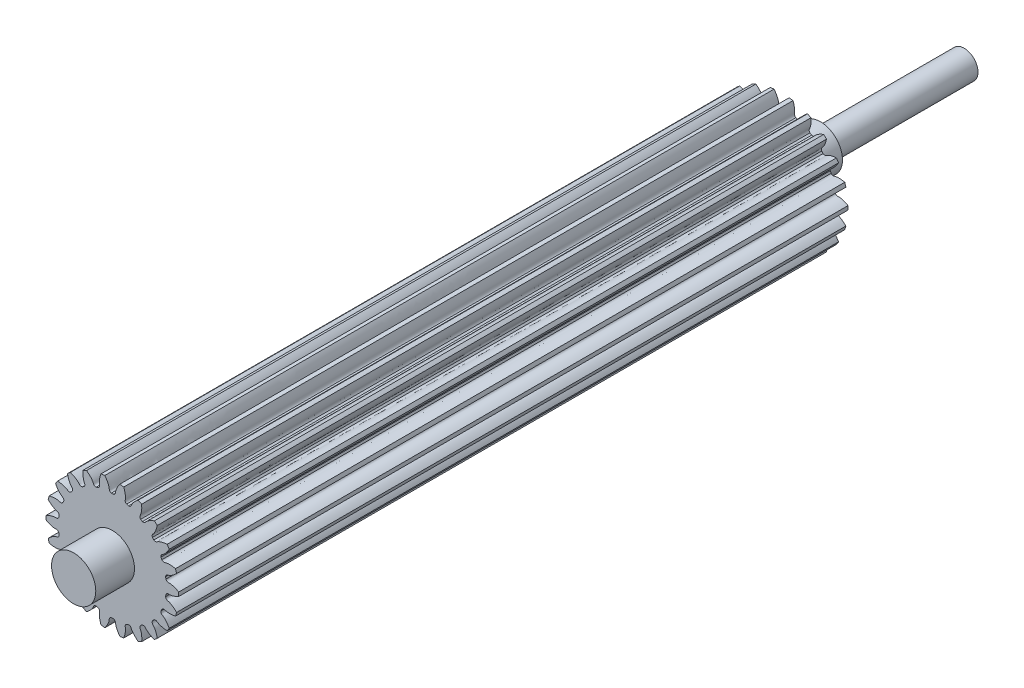
SolidWorks part; units mm, degrees
ref_plane "前视基准面" through (0, 0, 0) normal (0, 0, 1) x (1, 0, 0)
ref_plane "上视基准面" through (0, 0, 0) normal (0, 1, 0) x (1, 0, 0)
ref_plane "右视基准面" through (0, 0, 0) normal (1, 0, 0) x (0, 0, -1)
sketch "草图1" plane through (0, 0, 0) normal (0, 0, 1) x (1, 0, 0)
  circle A0 centre (0, 0) radius 12
extrude "凸台-拉伸1" add sketch "草图1" along normal blind 30
ref_axis "基准轴1" through (0, 0, -1.5) along (0, 0, 1)
sketch "草图2" plane through (0, 0, 0) normal (0, 0, 1) x (1, 0, 0)
  line L0 (0, 0) -> (0, 12) construction
  circle A0 centre (0, 0) radius 12 construction
  arc A1 (0.1857, 9.7482) -> (-0.1857, 9.7482) centre (0, 0) ccw
  arc A2 (3.0856, 13.5599) -> (-3.0856, 13.5599) centre (0, 0) ccw
  spline S0 degree 3 poles (0.1857, 9.7482) (0.5882, 9.8762) (0.5483, 10.1518) (0.5996, 10.4216) (0.606, 10.4519) (0.6139, 10.4862) (0.6235, 10.5243) (0.6349, 10.5661) (0.6484, 10.6117) (0.664, 10.661) (0.6819, 10.7139) (0.7023, 10.7703) (0.7253, 10.8301) (0.7511, 10.8933) (0.7797, 10.9597) (0.8114, 11.0293) (0.8462, 11.1021) (0.8843, 11.1778) (0.9259, 11.2563) (0.9711, 11.3377) (1.0199, 11.4217) (1.0726, 11.5082) (1.1292, 11.5972) (1.1899, 11.6884) (1.2547, 11.7818) (1.3238, 11.8773) (1.3973, 11.9746) (1.4753, 12.0737) (1.5579, 12.1744) (1.6452, 12.2766) (1.7372, 12.3802) (1.8341, 12.4849) (1.9359, 12.5906) (2.0428, 12.6972) (2.1547, 12.8044) (2.2718, 12.9123) (2.3942, 13.0205) (2.5218, 13.1289) (2.6548, 13.2373) (2.8415, 13.3834) (2.9864, 13.49) (3.0856, 13.5599) knots 0 0 0 0 0.157021 0.162531 0.168888 0.176093 0.184146 0.193046 0.202794 0.213389 0.224833 0.237123 0.250262 0.264248 0.279082 0.294763 0.311292 0.328669 0.346893 0.365965 0.385884 0.406652 0.428266 0.450729 0.474039 0.498197 0.523202 0.549055 0.575756 0.603304 0.6317 0.660944 0.691035 0.721974 0.75376 0.786395 0.819876 0.854206 0.889383 0.925408 1 1 1 1
  spline S1 degree 3 poles (-0.1857, 9.7482) (-0.5882, 9.8762) (-0.5483, 10.1518) (-0.5996, 10.4216) (-0.606, 10.4519) (-0.6139, 10.4862) (-0.6235, 10.5243) (-0.6349, 10.5661) (-0.6484, 10.6117) (-0.664, 10.661) (-0.6819, 10.7139) (-0.7023, 10.7703) (-0.7253, 10.8301) (-0.7511, 10.8933) (-0.7797, 10.9597) (-0.8114, 11.0293) (-0.8462, 11.1021) (-0.8843, 11.1778) (-0.9259, 11.2563) (-0.9711, 11.3377) (-1.0199, 11.4217) (-1.0726, 11.5082) (-1.1292, 11.5972) (-1.1899, 11.6884) (-1.2547, 11.7818) (-1.3238, 11.8773) (-1.3973, 11.9746) (-1.4753, 12.0737) (-1.5579, 12.1744) (-1.6452, 12.2766) (-1.7372, 12.3802) (-1.8341, 12.4849) (-1.9359, 12.5906) (-2.0428, 12.6972) (-2.1547, 12.8044) (-2.2718, 12.9123) (-2.3942, 13.0205) (-2.5218, 13.1289) (-2.6548, 13.2373) (-2.8415, 13.3834) (-2.9864, 13.49) (-3.0856, 13.5599) knots 0 0 0 0 0.157021 0.162531 0.168888 0.176093 0.184146 0.193046 0.202794 0.213389 0.224833 0.237123 0.250262 0.264248 0.279082 0.294763 0.311292 0.328669 0.346893 0.365965 0.385884 0.406652 0.428266 0.450729 0.474039 0.498197 0.523202 0.549055 0.575756 0.603304 0.6317 0.660944 0.691035 0.721974 0.75376 0.786395 0.819876 0.854206 0.889383 0.925408 1 1 1 1
extrude "切除-拉伸1" cut sketch "草图2" along normal through all
pattern_circular "阵列(圆周)1" count 22 every 16.364 about axis through (0, 0, -1.5) along (0, 0, 1) of "切除-拉伸1"
sketch "草图3" plane through (0, 0, 0) normal (0, 0, 1) x (1, 0, 0)
  circle A0 centre (0, 0) radius 11 construction
  dimension "Dn" = 22
sketch "草图4" plane through (0, 0, 0) normal (0, 0, -1) x (-1, 0, 0)
  arc A45 (2.9245, 9.3011) -> (2.5682, 9.4057) centre (0, 0) ccw
  arc A46 (2.0557, 11.8226) -> (1.3584, 11.9229) centre (0, 0) ccw
  arc A47 (0.1857, 9.7482) -> (-0.1857, 9.7482) centre (0, 0) ccw
  arc A48 (-1.3584, 11.9229) -> (-2.0557, 11.8226) centre (0, 0) ccw
  arc A49 (-2.5682, 9.4057) -> (-2.9245, 9.3011) centre (0, 0) ccw
  arc A50 (-4.6624, 11.0572) -> (-5.3032, 10.7646) centre (0, 0) ccw
  arc A51 (-5.1141, 8.3011) -> (-5.4265, 8.1004) centre (0, 0) ccw
  arc A52 (-7.5887, 9.2958) -> (-8.1211, 8.8344) centre (0, 0) ccw
  arc A53 (-7.2456, 6.5241) -> (-7.4888, 6.2434) centre (0, 0) ccw
  arc A54 (-9.9003, 6.7812) -> (-10.2811, 6.1886) centre (0, 0) ccw
  arc A55 (-8.7902, 4.2184) -> (-8.9444, 3.8807) centre (0, 0) ccw
  arc A56 (-11.4097, 3.7173) -> (-11.6082, 3.0414) centre (0, 0) ccw
  arc A57 (-9.6226, 1.5711) -> (-9.6754, 1.2035) centre (0, 0) ccw
  arc A58 (-11.9948, 0.3522) -> (-11.9948, -0.3522) centre (0, 0) ccw
  arc A59 (-9.6754, -1.2035) -> (-9.6226, -1.5711) centre (0, 0) ccw
  arc A60 (-11.6082, -3.0414) -> (-11.4097, -3.7173) centre (0, 0) ccw
  arc A61 (-8.9444, -3.8807) -> (-8.7902, -4.2184) centre (0, 0) ccw
  arc A62 (-10.2811, -6.1886) -> (-9.9003, -6.7812) centre (0, 0) ccw
  arc A63 (-7.4888, -6.2434) -> (-7.2456, -6.5241) centre (0, 0) ccw
  arc A64 (-8.1211, -8.8344) -> (-7.5887, -9.2958) centre (0, 0) ccw
  arc A65 (-5.4265, -8.1004) -> (-5.1141, -8.3011) centre (0, 0) ccw
  arc A66 (-5.3032, -10.7646) -> (-4.6624, -11.0572) centre (0, 0) ccw
  arc A67 (-2.9245, -9.3011) -> (-2.5682, -9.4057) centre (0, 0) ccw
  arc A68 (-2.0557, -11.8226) -> (-1.3584, -11.9229) centre (0, 0) ccw
  arc A69 (-0.1857, -9.7482) -> (0.1857, -9.7482) centre (0, 0) ccw
  arc A70 (1.3584, -11.9229) -> (2.0557, -11.8226) centre (0, 0) ccw
  arc A71 (2.5682, -9.4057) -> (2.9245, -9.3011) centre (0, 0) ccw
  arc A72 (4.6624, -11.0572) -> (5.3032, -10.7646) centre (0, 0) ccw
  arc A73 (5.1141, -8.3011) -> (5.4265, -8.1004) centre (0, 0) ccw
  arc A74 (7.5887, -9.2958) -> (8.1211, -8.8344) centre (0, 0) ccw
  arc A75 (7.2456, -6.5241) -> (7.4888, -6.2434) centre (0, 0) ccw
  arc A76 (9.9003, -6.7812) -> (10.2811, -6.1886) centre (0, 0) ccw
  arc A77 (8.7902, -4.2184) -> (8.9444, -3.8807) centre (0, 0) ccw
  arc A78 (11.4097, -3.7173) -> (11.6082, -3.0414) centre (0, 0) ccw
  arc A79 (9.6226, -1.5711) -> (9.6754, -1.2035) centre (0, 0) ccw
  arc A80 (11.9948, -0.3522) -> (11.9948, 0.3522) centre (0, 0) ccw
  arc A81 (9.6754, 1.2035) -> (9.6226, 1.5711) centre (0, 0) ccw
  arc A82 (11.6082, 3.0414) -> (11.4097, 3.7173) centre (0, 0) ccw
  arc A83 (8.9444, 3.8807) -> (8.7902, 4.2184) centre (0, 0) ccw
  arc A84 (10.2811, 6.1886) -> (9.9003, 6.7812) centre (0, 0) ccw
  arc A85 (7.4888, 6.2434) -> (7.2456, 6.5241) centre (0, 0) ccw
  arc A86 (8.1211, 8.8344) -> (7.5887, 9.2958) centre (0, 0) ccw
  arc A87 (5.4265, 8.1004) -> (5.1141, 8.3011) centre (0, 0) ccw
  arc A88 (5.3032, 10.7646) -> (4.6624, 11.0572) centre (0, 0) ccw
  arc A89 (2.9245, 9.3011) -> (2.5682, 9.4057) centre (0, 0) ccw
  arc A90 (2.0557, 11.8226) -> (1.3584, 11.9229) centre (0, 0) ccw
  arc A91 (0.1857, 9.7482) -> (-0.1857, 9.7482) centre (0, 0) ccw
  arc A92 (-1.3584, 11.9229) -> (-2.0557, 11.8226) centre (0, 0) ccw
  arc A93 (-2.5682, 9.4057) -> (-2.9245, 9.3011) centre (0, 0) ccw
  arc A94 (-4.6624, 11.0572) -> (-5.3032, 10.7646) centre (0, 0) ccw
  arc A95 (-5.1141, 8.3011) -> (-5.4265, 8.1004) centre (0, 0) ccw
  arc A96 (-7.5887, 9.2958) -> (-8.1211, 8.8344) centre (0, 0) ccw
  arc A97 (-7.2456, 6.5241) -> (-7.4888, 6.2434) centre (0, 0) ccw
  arc A98 (-9.9003, 6.7812) -> (-10.2811, 6.1886) centre (0, 0) ccw
  arc A99 (-8.7902, 4.2184) -> (-8.9444, 3.8807) centre (0, 0) ccw
  arc A100 (-11.4097, 3.7173) -> (-11.6082, 3.0414) centre (0, 0) ccw
  arc A101 (-9.6226, 1.5711) -> (-9.6754, 1.2035) centre (0, 0) ccw
  arc A102 (-11.9948, 0.3522) -> (-11.9948, -0.3522) centre (0, 0) ccw
  arc A103 (-9.6754, -1.2035) -> (-9.6226, -1.5711) centre (0, 0) ccw
  arc A104 (-11.6082, -3.0414) -> (-11.4097, -3.7173) centre (0, 0) ccw
  arc A105 (-8.9444, -3.8807) -> (-8.7902, -4.2184) centre (0, 0) ccw
  arc A106 (-10.2811, -6.1886) -> (-9.9003, -6.7812) centre (0, 0) ccw
  arc A107 (-7.4888, -6.2434) -> (-7.2456, -6.5241) centre (0, 0) ccw
  arc A108 (-8.1211, -8.8344) -> (-7.5887, -9.2958) centre (0, 0) ccw
  arc A109 (-5.4265, -8.1004) -> (-5.1141, -8.3011) centre (0, 0) ccw
  arc A110 (-5.3032, -10.7646) -> (-4.6624, -11.0572) centre (0, 0) ccw
  arc A111 (-2.9245, -9.3011) -> (-2.5682, -9.4057) centre (0, 0) ccw
  arc A112 (-2.0557, -11.8226) -> (-1.3584, -11.9229) centre (0, 0) ccw
  arc A113 (-0.1857, -9.7482) -> (0.1857, -9.7482) centre (0, 0) ccw
  arc A114 (1.3584, -11.9229) -> (2.0557, -11.8226) centre (0, 0) ccw
  arc A115 (2.5682, -9.4057) -> (2.9245, -9.3011) centre (0, 0) ccw
  arc A116 (4.6624, -11.0572) -> (5.3032, -10.7646) centre (0, 0) ccw
  arc A117 (5.1141, -8.3011) -> (5.4265, -8.1004) centre (0, 0) ccw
  arc A118 (7.5887, -9.2958) -> (8.1211, -8.8344) centre (0, 0) ccw
  arc A119 (7.2456, -6.5241) -> (7.4888, -6.2434) centre (0, 0) ccw
  arc A120 (9.9003, -6.7812) -> (10.2811, -6.1886) centre (0, 0) ccw
  arc A121 (8.7902, -4.2184) -> (8.9444, -3.8807) centre (0, 0) ccw
  arc A122 (11.4097, -3.7173) -> (11.6082, -3.0414) centre (0, 0) ccw
  arc A123 (9.6226, -1.5711) -> (9.6754, -1.2035) centre (0, 0) ccw
  arc A124 (11.9948, -0.3522) -> (11.9948, 0.3522) centre (0, 0) ccw
  arc A125 (9.6754, 1.2035) -> (9.6226, 1.5711) centre (0, 0) ccw
  arc A126 (11.6082, 3.0414) -> (11.4097, 3.7173) centre (0, 0) ccw
  arc A127 (8.9444, 3.8807) -> (8.7902, 4.2184) centre (0, 0) ccw
  arc A128 (10.2811, 6.1886) -> (9.9003, 6.7812) centre (0, 0) ccw
  arc A129 (7.4888, 6.2434) -> (7.2456, 6.5241) centre (0, 0) ccw
  arc A130 (8.1211, 8.8344) -> (7.5887, 9.2958) centre (0, 0) ccw
  arc A131 (5.4265, 8.1004) -> (5.1141, 8.3011) centre (0, 0) ccw
  arc A132 (5.3032, 10.7646) -> (4.6624, 11.0572) centre (0, 0) ccw
  spline S44 degree 3 poles (-7496.4592, 2789.5016) (226.4744, -158.9957) (28.5821, 31.5473) (4.2738, 10.7434) (4.1283, 10.6084) (3.9999, 10.4794) (3.888, 10.3576) (3.7917, 10.2441) (3.7102, 10.1398) (3.6518, 10.0587) (3.6037, 9.9872) (3.5713, 9.9359) (3.5381, 9.8795) (3.5167, 9.8409) (0.6369, 4.2172) (43.7494, -24.3223) (-6732.0995, 4323.7051) knots -19.040021 -19.040021 -19.040021 -19.040021 0.549271 0.593348 0.634035 0.671331 0.705237 0.735752 0.762877 0.786611 0.797206 0.815854 0.823907 0.837469 0.842979 4.709556 4.709556 4.709556 4.709556 only from (4.6624, 11.0572) to (2.9245, 9.3011)
  spline S45 degree 3 poles (7999.956, -2.3149) (-49.9496, 3.1915) (1.7443, 3.8923) (2.3619, 10.18) (2.3658, 10.2385) (2.3681, 10.3211) (2.3668, 10.4204) (2.3608, 10.536) (2.3486, 10.6678) (2.329, 10.8154) (2.3007, 10.9784) (2.2624, 11.1562) (2.213, 11.3485) (2.1511, 11.5544) (-8.9188, 43.6975) (-289.9121, -23.2582) (7822.5066, -1669.0431) knots -3.709393 -3.709393 -3.709393 -3.709393 0.157021 0.162531 0.176093 0.193046 0.213389 0.237123 0.264248 0.294763 0.328669 0.365965 0.406652 0.450729 0.498197 21.310868 21.310868 21.310868 21.310868 only from (2.5682, 9.4057) to (2.0557, 11.8226)
  spline S46 degree 3 poles (-7978.6933, 564.5106) (262.0949, -88.75) (18.5364, 38.3219) (1.0739, 11.5123) (0.9723, 11.3417) (0.8855, 11.1818) (0.8124, 11.0334) (0.752, 10.8973) (0.7032, 10.7743) (0.6701, 10.6801) (0.644, 10.5979) (0.6274, 10.5396) (0.6113, 10.4761) (0.6018, 10.4331) (-0.577, 4.2258) (48.8297, -11.0115) (-7677.5306, 2251.913) knots -19.040021 -19.040021 -19.040021 -19.040021 0.549271 0.593348 0.634035 0.671331 0.705237 0.735752 0.762877 0.786611 0.797206 0.815854 0.823907 0.837469 0.842979 4.709556 4.709556 4.709556 4.709556 only from (1.3584, 11.9229) to (0.1857, 9.7482)
  spline S47 degree 3 poles (7676.5537, 2251.6269) (-48.8255, -11.0102) (0.577, 4.2261) (-0.6018, 10.4331) (-0.6145, 10.4903) (-0.6356, 10.5702) (-0.6648, 10.6651) (-0.7032, 10.7743) (-0.752, 10.8973) (-0.8124, 11.0334) (-0.8855, 11.1818) (-0.9723, 11.3417) (-1.0739, 11.5123) (-1.1913, 11.6924) (-20.8685, 39.4148) (-271.616, -103.9938) (7975.8639, 602.4197) knots -3.709393 -3.709393 -3.709393 -3.709393 0.157021 0.162531 0.176093 0.193046 0.213389 0.237123 0.264248 0.294763 0.328669 0.365965 0.406652 0.450729 0.498197 21.310868 21.310868 21.310868 21.310868 only from (-0.1857, 9.7482) to (-1.3584, 11.9229)
  spline S48 degree 3 poles (-7814.5412, -1706.2138) (276.482, -11.3143) (6.989, 41.9919) (-2.213, 11.3485) (-2.2624, 11.1562) (-2.3007, 10.9784) (-2.329, 10.8154) (-2.3486, 10.6678) (-2.3608, 10.536) (-2.366, 10.4362) (-2.3678, 10.3501) (-2.3674, 10.2894) (-2.3649, 10.224) (-2.3619, 10.18) (-1.7442, 3.8921) (49.954, 3.1915) (-8000.9739, -2.3156) knots -19.040021 -19.040021 -19.040021 -19.040021 0.549271 0.593348 0.634035 0.671331 0.705237 0.735752 0.762877 0.786611 0.797206 0.815854 0.823907 0.837469 0.842979 4.709556 4.709556 4.709556 4.709556 only from (-2.0557, 11.8226) to (-2.5682, 9.4057)
  spline S49 degree 3 poles (6731.2428, 4323.1553) (-43.7458, -24.3199) (-0.637, 4.2175) (-3.5167, 9.8409) (-3.5451, 9.8922) (-3.5879, 9.963) (-3.6426, 10.0458) (-3.7102, 10.1398) (-3.7917, 10.2441) (-3.888, 10.3576) (-3.9999, 10.4794) (-4.1283, 10.6084) (-4.2738, 10.7434) (-4.4372, 10.8832) (-31.1276, 31.9389) (-231.3152, -176.3044) (7483.0641, 2825.078) knots -3.709393 -3.709393 -3.709393 -3.709393 0.157021 0.162531 0.176093 0.193046 0.213389 0.237123 0.264248 0.294763 0.328669 0.365965 0.406652 0.450729 0.498197 21.310868 21.310868 21.310868 21.310868 only from (-2.9245, 9.3011) to (-4.6624, 11.0572)
  spline S50 degree 3 poles (-7017.3014, -3838.7108) (268.4701, 67.0379) (-5.1246, 42.26) (-5.3206, 10.2653) (-5.3138, 10.0669) (-5.3004, 9.8855) (-5.2817, 9.7211) (-5.2589, 9.574) (-5.2335, 9.4441) (-5.2104, 9.3469) (-5.1879, 9.2637) (-5.1704, 9.2057) (-5.1495, 9.1436) (-5.1343, 9.1022) (-2.7701, 3.243) (47.0314, 17.1359) (-7676.2259, -2256.3566) knots -19.040021 -19.040021 -19.040021 -19.040021 0.549271 0.593348 0.634035 0.671331 0.705237 0.735752 0.762877 0.786611 0.797206 0.815854 0.823907 0.837469 0.842979 4.709556 4.709556 4.709556 4.709556 only from (-5.3032, 10.7646) to (-5.1141, 8.3011)
  spline S51 degree 3 poles (5240.6065, 6044.4474) (-35.1221, -35.6594) (-1.7994, 3.8672) (-6.1468, 8.4515) (-6.1884, 8.4928) (-6.2494, 8.5486) (-6.3253, 8.6126) (-6.4166, 8.6838) (-6.5242, 8.7609) (-6.6486, 8.8427) (-6.7903, 8.928) (-6.9498, 9.0156) (-7.1274, 9.1041) (-7.3236, 9.1923) (-38.865, 21.8754) (-172.2747, -234.3319) (6384.031, 4818.8653) knots -3.709393 -3.709393 -3.709393 -3.709393 0.157021 0.162531 0.176093 0.193046 0.213389 0.237123 0.264248 0.294763 0.328669 0.365965 0.406652 0.450729 0.498197 21.310868 21.310868 21.310868 21.310868 only from (-5.4265, 8.1004) to (-7.5887, 9.2958)
  spline S52 degree 3 poles (-5651.5616, -5660.2183) (238.7084, 139.9592) (-16.823, 39.1044) (-7.9971, 8.3505) (-7.9348, 8.1621) (-7.8708, 7.9917) (-7.8065, 7.8393) (-7.7432, 7.7046) (-7.6822, 7.5871) (-7.6327, 7.5003) (-7.5876, 7.4269) (-7.5545, 7.3761) (-7.517, 7.3224) (-7.4907, 7.287) (-3.5716, 2.3312) (40.2985, 29.692) (-6729.5957, -4327.6011) knots -19.040021 -19.040021 -19.040021 -19.040021 0.549271 0.593348 0.634035 0.671331 0.705237 0.735752 0.762877 0.786611 0.797206 0.815854 0.823907 0.837469 0.842979 4.709556 4.709556 4.709556 4.709556 only from (-8.1211, 8.8344) to (-7.2456, 6.5241)
  spline S53 degree 3 poles (3325.4075, 7276.0543) (-23.653, -44.11) (-2.816, 3.2036) (-8.2789, 6.3774) (-8.3304, 6.4053) (-8.4047, 6.4416) (-8.4955, 6.4817) (-8.6032, 6.5243) (-8.7281, 6.5679) (-8.8705, 6.6114) (-9.0305, 6.6533) (-9.2082, 6.6924) (-9.4036, 6.7273) (-9.6167, 6.7566) (-43.4537, 10.0398) (-99.2774, -273.3752) (4767.8017, 6422.2568) knots -3.709393 -3.709393 -3.709393 -3.709393 0.157021 0.162531 0.176093 0.193046 0.213389 0.237123 0.264248 0.294763 0.328669 0.365965 0.406652 0.450729 0.498197 21.310868 21.310868 21.310868 21.310868 only from (-7.4888, 6.2434) to (-9.9003, 6.7812)
  spline S54 degree 3 poles (-3827.9659, -7023.1686) (189.608, 201.5418) (-27.1586, 32.7808) (-10.0258, 5.7592) (-9.9129, 5.596) (-9.8035, 5.4506) (-9.6989, 5.3224) (-9.6002, 5.211) (-9.5086, 5.1155) (-9.4366, 5.0462) (-9.3727, 4.9884) (-9.3266, 4.949) (-9.2755, 4.908) (-9.2403, 4.8814) (-4.0837, 1.2306) (30.3009, 39.8427) (-5237.7736, -6048.249) knots -19.040021 -19.040021 -19.040021 -19.040021 0.549271 0.593348 0.634035 0.671331 0.705237 0.735752 0.762877 0.786611 0.797206 0.815854 0.823907 0.837469 0.842979 4.709556 4.709556 4.709556 4.709556 only from (-10.2811, 6.1886) to (-8.7902, 4.2184)
  spline S55 degree 3 poles (1140.8038, 7918.1985) (-10.2676, -48.987) (-3.6045, 2.2804) (-9.7402, 3.7867) (-9.7976, 3.7989) (-9.8791, 3.8128) (-9.9775, 3.8257) (-10.0928, 3.8362) (-10.225, 3.8429) (-10.3738, 3.8445) (-10.5392, 3.8396) (-10.7207, 3.8271) (-10.918, 3.8055) (-11.1307, 3.7736) (-44.522, -2.6092) (-18.2373, -290.2712) (2765.3134, 7505.3552) knots -3.709393 -3.709393 -3.709393 -3.709393 0.157021 0.162531 0.176093 0.193046 0.213389 0.237123 0.264248 0.294763 0.328669 0.365965 0.406652 0.450729 0.498197 21.310868 21.310868 21.310868 21.310868 only from (-8.9444, 3.8807) to (-11.4097, 3.7173)
  spline S56 degree 3 poles (-1694.2511, -7817.1435) (125.1466, 246.7967) (-35.2939, 23.8015) (-11.2422, 2.7013) (-11.0879, 2.5765) (-10.942, 2.4678) (-10.8055, 2.3743) (-10.6794, 2.2952) (-10.5646, 2.2294) (-10.476, 2.1832) (-10.3984, 2.1457) (-10.3431, 2.1209) (-10.2825, 2.096) (-10.2412, 2.0804) (-4.2649, 0.0302) (17.8486, 46.7655) (-3321.6183, -7278.9038) knots -19.040021 -19.040021 -19.040021 -19.040021 0.549271 0.593348 0.634035 0.671331 0.705237 0.735752 0.762877 0.786611 0.797206 0.815854 0.823907 0.837469 0.842979 4.709556 4.709556 4.709556 4.709556 only from (-11.6082, 3.0414) to (-9.6226, 1.5711)
  spline S57 degree 3 poles (-1136.2211, 7918.8574) (3.9495, -49.8954) (-4.101, 1.1726) (-10.4125, 0.8891) (-10.4709, 0.8847) (-10.5531, 0.8751) (-10.6512, 0.8598) (-10.7647, 0.8373) (-10.8934, 0.8065) (-11.0367, 0.7661) (-11.194, 0.7149) (-11.3647, 0.6517) (-11.5479, 0.5754) (-11.743, 0.4849) (-41.9835, -15.0468) (64.2803, -283.6512) (538.7958, 7980.4144) knots -3.709393 -3.709393 -3.709393 -3.709393 0.157021 0.162531 0.176093 0.193046 0.213389 0.237123 0.264248 0.294763 0.328669 0.365965 0.406652 0.450729 0.498197 21.310868 21.310868 21.310868 21.310868 only from (-9.6754, 1.2035) to (-11.9948, 0.3522)
  spline S58 degree 3 poles (576.7218, -7977.82) (50.5467, 272.0576) (-40.5699, 12.894) (-11.5479, -0.5754) (-11.3647, -0.6517) (-11.194, -0.7149) (-11.0367, -0.7661) (-10.8934, -0.8065) (-10.7647, -0.8373) (-10.6667, -0.8567) (-10.5817, -0.8708) (-10.5216, -0.879) (-10.4565, -0.8858) (-10.4125, -0.8891) (-4.1007, -1.1726) (3.9502, 49.8997) (-1136.3653, -7919.8651) knots -19.040021 -19.040021 -19.040021 -19.040021 0.549271 0.593348 0.634035 0.671331 0.705237 0.735752 0.762877 0.786611 0.797206 0.815854 0.823907 0.837469 0.842979 4.709556 4.709556 4.709556 4.709556 only from (-11.9948, -0.3522) to (-9.6754, -1.2035)
  spline S59 degree 3 poles (-3321.1961, 7277.9776) (17.8467, -46.7616) (-4.2652, -0.0303) (-10.2412, -2.0804) (-10.296, -2.1012) (-10.3722, -2.1335) (-10.4619, -2.1758) (-10.5646, -2.2294) (-10.6794, -2.2952) (-10.8055, -2.3743) (-10.942, -2.4678) (-11.0879, -2.5765) (-11.2422, -2.7014) (-11.4039, -2.8432) (-36.0437, -26.2654) (141.5903, -254.0515) (-1731.3717, 7808.9478) knots -3.709393 -3.709393 -3.709393 -3.709393 0.157021 0.162531 0.176093 0.193046 0.213389 0.237123 0.264248 0.294763 0.328669 0.365965 0.406652 0.450729 0.498197 21.310868 21.310868 21.310868 21.310868 only from (-9.6226, -1.5711) to (-11.6082, -3.0414)
  spline S60 degree 3 poles (2800.9721, -7492.1809) (-28.1483, 275.278) (-42.5592, 0.9418) (-10.918, -3.8055) (-10.7207, -3.8271) (-10.5392, -3.8396) (-10.3738, -3.8445) (-10.225, -3.8429) (-10.0928, -3.8362) (-9.9933, -3.8272) (-9.9078, -3.8167) (-9.8478, -3.8076) (-9.7834, -3.7958) (-9.7402, -3.7867) (-3.6042, -2.2804) (-10.2682, 48.9913) (1140.9493, -7919.206) knots -19.040021 -19.040021 -19.040021 -19.040021 0.549271 0.593348 0.634035 0.671331 0.705237 0.735752 0.762877 0.786611 0.797206 0.815854 0.823907 0.837469 0.842979 4.709556 4.709556 4.709556 4.709556 only from (-11.4097, -3.7173) to (-8.9444, -3.8807)
  spline S61 degree 3 poles (-5237.1076, 6047.4793) (30.2981, -39.8394) (-4.0839, -1.2307) (-9.2403, -4.8814) (-9.287, -4.9168) (-9.351, -4.9692) (-9.4251, -5.0352) (-9.5086, -5.1155) (-9.6002, -5.211) (-9.6989, -5.3224) (-9.8035, -5.4506) (-9.9129, -5.596) (-10.0258, -5.7592) (-10.1409, -5.9408) (-27.1838, -35.3562) (207.4295, -203.8701) (-3861.2738, 7004.8468) knots -3.709393 -3.709393 -3.709393 -3.709393 0.157021 0.162531 0.176093 0.193046 0.213389 0.237123 0.264248 0.294763 0.328669 0.365965 0.406652 0.450729 0.498197 21.310868 21.310868 21.310868 21.310868 only from (-8.7902, -4.2184) to (-10.2811, -6.1886)
  spline S62 degree 3 poles (4798.3044, -6399.5699) (-104.5629, 256.197) (-41.1006, -11.0867) (-9.4036, -6.7273) (-9.2082, -6.6924) (-9.0305, -6.6533) (-8.8705, -6.6114) (-8.7281, -6.5679) (-8.6032, -6.5243) (-8.5102, -6.4876) (-8.4311, -6.4535) (-8.3761, -6.4279) (-8.3177, -6.3984) (-8.2789, -6.3774) (-2.8158, -3.2034) (-23.6547, 44.114) (3325.831, -7276.9799) knots -19.040021 -19.040021 -19.040021 -19.040021 0.549271 0.593348 0.634035 0.671331 0.705237 0.735752 0.762877 0.786611 0.797206 0.815854 0.823907 0.837469 0.842979 4.709556 4.709556 4.709556 4.709556 only from (-9.9003, -6.7812) to (-7.4888, -6.2434)
  spline S63 degree 3 poles (-6728.7397, 4327.0502) (40.2948, -29.6897) (-3.5717, -2.3314) (-7.4907, -7.287) (-7.5256, -7.3341) (-7.5722, -7.4024) (-7.6248, -7.4866) (-7.6822, -7.5871) (-7.7432, -7.7046) (-7.8065, -7.8393) (-7.8708, -7.9917) (-7.9348, -8.1621) (-7.9971, -8.3505) (-8.0564, -8.5572) (-16.1217, -41.5826) (256.4639, -137.1723) (-5678.3585, 5633.2547) knots -3.709393 -3.709393 -3.709393 -3.709393 0.157021 0.162531 0.176093 0.193046 0.213389 0.237123 0.264248 0.294763 0.328669 0.365965 0.406652 0.450729 0.498197 21.310868 21.310868 21.310868 21.310868 only from (-7.2456, -6.5241) to (-8.1211, -8.8344)
  spline S64 degree 3 poles (6406.9065, -4788.5038) (-172.5064, 216.3604) (-36.3122, -22.2169) (-7.1274, -9.1041) (-6.9498, -9.0156) (-6.7903, -8.928) (-6.6486, -8.8427) (-6.5242, -8.7609) (-6.4166, -8.6838) (-6.3378, -8.6224) (-6.2715, -8.5674) (-6.2259, -8.5273) (-6.1781, -8.4826) (-6.1468, -8.4515) (-1.7992, -3.867) (-35.1249, 35.6627) (5241.2736, -6045.2162) knots -19.040021 -19.040021 -19.040021 -19.040021 0.549271 0.593348 0.634035 0.671331 0.705237 0.735752 0.762877 0.786611 0.797206 0.815854 0.823907 0.837469 0.842979 4.709556 4.709556 4.709556 4.709556 only from (-7.5887, -9.2958) to (-5.4265, -8.1004)
  spline S65 degree 3 poles (-7675.2494, 2256.0692) (47.0272, -17.1347) (-2.7702, -3.2433) (-5.1343, -9.1022) (-5.1545, -9.1572) (-5.18, -9.2359) (-5.2067, -9.3315) (-5.2335, -9.4441) (-5.2589, -9.574) (-5.2817, -9.7211) (-5.3004, -9.8855) (-5.3138, -10.0669) (-5.3206, -10.2653) (-5.3192, -10.4804) (-3.7535, -44.4402) (284.7212, -59.3616) (-7035.4164, 3805.2899) knots -3.709393 -3.709393 -3.709393 -3.709393 0.157021 0.162531 0.176093 0.193046 0.213389 0.237123 0.264248 0.294763 0.328669 0.365965 0.406652 0.450729 0.498197 21.310868 21.310868 21.310868 21.310868 only from (-5.1141, -8.3011) to (-5.3032, -10.7646)
  spline S66 degree 3 poles (7496.4592, -2789.5016) (-226.4744, 158.9957) (-28.5821, -31.5473) (-4.2738, -10.7434) (-4.1283, -10.6084) (-3.9999, -10.4794) (-3.888, -10.3576) (-3.7917, -10.2441) (-3.7102, -10.1398) (-3.6518, -10.0587) (-3.6037, -9.9872) (-3.5713, -9.9359) (-3.5381, -9.8795) (-3.5167, -9.8409) (-0.6369, -4.2172) (-43.7494, 24.3223) (6732.0995, -4323.7051) knots -19.040021 -19.040021 -19.040021 -19.040021 0.549271 0.593348 0.634035 0.671331 0.705237 0.735752 0.762877 0.786611 0.797206 0.815854 0.823907 0.837469 0.842979 4.709556 4.709556 4.709556 4.709556 only from (-4.6624, -11.0572) to (-2.9245, -9.3011)
  spline S67 degree 3 poles (-7999.956, 2.3149) (49.9496, -3.1915) (-1.7443, -3.8923) (-2.3619, -10.18) (-2.3658, -10.2385) (-2.3681, -10.3211) (-2.3668, -10.4204) (-2.3608, -10.536) (-2.3486, -10.6678) (-2.329, -10.8154) (-2.3007, -10.9784) (-2.2624, -11.1562) (-2.213, -11.3485) (-2.1511, -11.5544) (8.9188, -43.6975) (289.9121, 23.2582) (-7822.5066, 1669.0431) knots -3.709393 -3.709393 -3.709393 -3.709393 0.157021 0.162531 0.176093 0.193046 0.213389 0.237123 0.264248 0.294763 0.328669 0.365965 0.406652 0.450729 0.498197 21.310868 21.310868 21.310868 21.310868 only from (-2.5682, -9.4057) to (-2.0557, -11.8226)
  spline S68 degree 3 poles (7978.6933, -564.5106) (-262.0949, 88.75) (-18.5364, -38.3219) (-1.0739, -11.5123) (-0.9723, -11.3417) (-0.8855, -11.1818) (-0.8124, -11.0334) (-0.752, -10.8973) (-0.7032, -10.7743) (-0.6701, -10.6801) (-0.644, -10.5979) (-0.6274, -10.5396) (-0.6113, -10.4761) (-0.6018, -10.4331) (0.577, -4.2258) (-48.8297, 11.0115) (7677.5306, -2251.913) knots -19.040021 -19.040021 -19.040021 -19.040021 0.549271 0.593348 0.634035 0.671331 0.705237 0.735752 0.762877 0.786611 0.797206 0.815854 0.823907 0.837469 0.842979 4.709556 4.709556 4.709556 4.709556 only from (-1.3584, -11.9229) to (-0.1857, -9.7482)
  spline S69 degree 3 poles (-7676.5537, -2251.6269) (48.8255, 11.0102) (-0.577, -4.2261) (0.6018, -10.4331) (0.6145, -10.4903) (0.6356, -10.5702) (0.6648, -10.6651) (0.7032, -10.7743) (0.752, -10.8973) (0.8124, -11.0334) (0.8855, -11.1818) (0.9723, -11.3417) (1.0739, -11.5123) (1.1913, -11.6924) (20.8685, -39.4148) (271.616, 103.9938) (-7975.8639, -602.4197) knots -3.709393 -3.709393 -3.709393 -3.709393 0.157021 0.162531 0.176093 0.193046 0.213389 0.237123 0.264248 0.294763 0.328669 0.365965 0.406652 0.450729 0.498197 21.310868 21.310868 21.310868 21.310868 only from (0.1857, -9.7482) to (1.3584, -11.9229)
  spline S70 degree 3 poles (7814.5412, 1706.2138) (-276.482, 11.3143) (-6.989, -41.9919) (2.213, -11.3485) (2.2624, -11.1562) (2.3007, -10.9784) (2.329, -10.8154) (2.3486, -10.6678) (2.3608, -10.536) (2.366, -10.4362) (2.3678, -10.3501) (2.3674, -10.2894) (2.3649, -10.224) (2.3619, -10.18) (1.7442, -3.8921) (-49.954, -3.1915) (8000.9739, 2.3156) knots -19.040021 -19.040021 -19.040021 -19.040021 0.549271 0.593348 0.634035 0.671331 0.705237 0.735752 0.762877 0.786611 0.797206 0.815854 0.823907 0.837469 0.842979 4.709556 4.709556 4.709556 4.709556 only from (2.0557, -11.8226) to (2.5682, -9.4057)
  spline S71 degree 3 poles (-6731.2428, -4323.1553) (43.7458, 24.3199) (0.637, -4.2175) (3.5167, -9.8409) (3.5451, -9.8922) (3.5879, -9.963) (3.6426, -10.0458) (3.7102, -10.1398) (3.7917, -10.2441) (3.888, -10.3576) (3.9999, -10.4794) (4.1283, -10.6084) (4.2738, -10.7434) (4.4372, -10.8832) (31.1276, -31.9389) (231.3152, 176.3044) (-7483.0641, -2825.078) knots -3.709393 -3.709393 -3.709393 -3.709393 0.157021 0.162531 0.176093 0.193046 0.213389 0.237123 0.264248 0.294763 0.328669 0.365965 0.406652 0.450729 0.498197 21.310868 21.310868 21.310868 21.310868 only from (2.9245, -9.3011) to (4.6624, -11.0572)
  spline S72 degree 3 poles (7017.3014, 3838.7108) (-268.4701, -67.0379) (5.1246, -42.26) (5.3206, -10.2653) (5.3138, -10.0669) (5.3004, -9.8855) (5.2817, -9.7211) (5.2589, -9.574) (5.2335, -9.4441) (5.2104, -9.3469) (5.1879, -9.2637) (5.1704, -9.2057) (5.1495, -9.1436) (5.1343, -9.1022) (2.7701, -3.243) (-47.0314, -17.1359) (7676.2259, 2256.3566) knots -19.040021 -19.040021 -19.040021 -19.040021 0.549271 0.593348 0.634035 0.671331 0.705237 0.735752 0.762877 0.786611 0.797206 0.815854 0.823907 0.837469 0.842979 4.709556 4.709556 4.709556 4.709556 only from (5.3032, -10.7646) to (5.1141, -8.3011)
  spline S73 degree 3 poles (-5240.6065, -6044.4474) (35.1221, 35.6594) (1.7994, -3.8672) (6.1468, -8.4515) (6.1884, -8.4928) (6.2494, -8.5486) (6.3253, -8.6126) (6.4166, -8.6838) (6.5242, -8.7609) (6.6486, -8.8427) (6.7903, -8.928) (6.9498, -9.0156) (7.1274, -9.1041) (7.3236, -9.1923) (38.865, -21.8754) (172.2747, 234.3319) (-6384.031, -4818.8653) knots -3.709393 -3.709393 -3.709393 -3.709393 0.157021 0.162531 0.176093 0.193046 0.213389 0.237123 0.264248 0.294763 0.328669 0.365965 0.406652 0.450729 0.498197 21.310868 21.310868 21.310868 21.310868 only from (5.4265, -8.1004) to (7.5887, -9.2958)
  spline S74 degree 3 poles (5651.5616, 5660.2183) (-238.7084, -139.9592) (16.823, -39.1044) (7.9971, -8.3505) (7.9348, -8.1621) (7.8708, -7.9917) (7.8065, -7.8393) (7.7432, -7.7046) (7.6822, -7.5871) (7.6327, -7.5003) (7.5876, -7.4269) (7.5545, -7.3761) (7.517, -7.3224) (7.4907, -7.287) (3.5716, -2.3312) (-40.2985, -29.692) (6729.5957, 4327.6011) knots -19.040021 -19.040021 -19.040021 -19.040021 0.549271 0.593348 0.634035 0.671331 0.705237 0.735752 0.762877 0.786611 0.797206 0.815854 0.823907 0.837469 0.842979 4.709556 4.709556 4.709556 4.709556 only from (8.1211, -8.8344) to (7.2456, -6.5241)
  spline S75 degree 3 poles (-3325.4075, -7276.0543) (23.653, 44.11) (2.816, -3.2036) (8.2789, -6.3774) (8.3304, -6.4053) (8.4047, -6.4416) (8.4955, -6.4817) (8.6032, -6.5243) (8.7281, -6.5679) (8.8705, -6.6114) (9.0305, -6.6533) (9.2082, -6.6924) (9.4036, -6.7273) (9.6167, -6.7566) (43.4537, -10.0398) (99.2774, 273.3752) (-4767.8017, -6422.2568) knots -3.709393 -3.709393 -3.709393 -3.709393 0.157021 0.162531 0.176093 0.193046 0.213389 0.237123 0.264248 0.294763 0.328669 0.365965 0.406652 0.450729 0.498197 21.310868 21.310868 21.310868 21.310868 only from (7.4888, -6.2434) to (9.9003, -6.7812)
  spline S76 degree 3 poles (3827.9659, 7023.1686) (-189.608, -201.5418) (27.1586, -32.7808) (10.0258, -5.7592) (9.9129, -5.596) (9.8035, -5.4506) (9.6989, -5.3224) (9.6002, -5.211) (9.5086, -5.1155) (9.4366, -5.0462) (9.3727, -4.9884) (9.3266, -4.949) (9.2755, -4.908) (9.2403, -4.8814) (4.0837, -1.2306) (-30.3009, -39.8427) (5237.7736, 6048.249) knots -19.040021 -19.040021 -19.040021 -19.040021 0.549271 0.593348 0.634035 0.671331 0.705237 0.735752 0.762877 0.786611 0.797206 0.815854 0.823907 0.837469 0.842979 4.709556 4.709556 4.709556 4.709556 only from (10.2811, -6.1886) to (8.7902, -4.2184)
  spline S77 degree 3 poles (-1140.8038, -7918.1985) (10.2676, 48.987) (3.6045, -2.2804) (9.7402, -3.7867) (9.7976, -3.7989) (9.8791, -3.8128) (9.9775, -3.8257) (10.0928, -3.8362) (10.225, -3.8429) (10.3738, -3.8445) (10.5392, -3.8396) (10.7207, -3.8271) (10.918, -3.8055) (11.1307, -3.7736) (44.522, 2.6092) (18.2373, 290.2712) (-2765.3134, -7505.3552) knots -3.709393 -3.709393 -3.709393 -3.709393 0.157021 0.162531 0.176093 0.193046 0.213389 0.237123 0.264248 0.294763 0.328669 0.365965 0.406652 0.450729 0.498197 21.310868 21.310868 21.310868 21.310868 only from (8.9444, -3.8807) to (11.4097, -3.7173)
  spline S78 degree 3 poles (1694.2511, 7817.1435) (-125.1466, -246.7967) (35.2939, -23.8015) (11.2422, -2.7013) (11.0879, -2.5765) (10.942, -2.4678) (10.8055, -2.3743) (10.6794, -2.2952) (10.5646, -2.2294) (10.476, -2.1832) (10.3984, -2.1457) (10.3431, -2.1209) (10.2825, -2.096) (10.2412, -2.0804) (4.2649, -0.0302) (-17.8486, -46.7655) (3321.6183, 7278.9038) knots -19.040021 -19.040021 -19.040021 -19.040021 0.549271 0.593348 0.634035 0.671331 0.705237 0.735752 0.762877 0.786611 0.797206 0.815854 0.823907 0.837469 0.842979 4.709556 4.709556 4.709556 4.709556 only from (11.6082, -3.0414) to (9.6226, -1.5711)
  spline S79 degree 3 poles (1136.2211, -7918.8574) (-3.9495, 49.8954) (4.101, -1.1726) (10.4125, -0.8891) (10.4709, -0.8847) (10.5531, -0.8751) (10.6512, -0.8598) (10.7647, -0.8373) (10.8934, -0.8065) (11.0367, -0.7661) (11.194, -0.7149) (11.3647, -0.6517) (11.5479, -0.5754) (11.743, -0.4849) (41.9835, 15.0468) (-64.2803, 283.6512) (-538.7958, -7980.4144) knots -3.709393 -3.709393 -3.709393 -3.709393 0.157021 0.162531 0.176093 0.193046 0.213389 0.237123 0.264248 0.294763 0.328669 0.365965 0.406652 0.450729 0.498197 21.310868 21.310868 21.310868 21.310868 only from (9.6754, -1.2035) to (11.9948, -0.3522)
  spline S80 degree 3 poles (-576.7218, 7977.82) (-50.5467, -272.0576) (40.5699, -12.894) (11.5479, 0.5754) (11.3647, 0.6517) (11.194, 0.7149) (11.0367, 0.7661) (10.8934, 0.8065) (10.7647, 0.8373) (10.6667, 0.8567) (10.5817, 0.8708) (10.5216, 0.879) (10.4565, 0.8858) (10.4125, 0.8891) (4.1007, 1.1726) (-3.9502, -49.8997) (1136.3653, 7919.8651) knots -19.040021 -19.040021 -19.040021 -19.040021 0.549271 0.593348 0.634035 0.671331 0.705237 0.735752 0.762877 0.786611 0.797206 0.815854 0.823907 0.837469 0.842979 4.709556 4.709556 4.709556 4.709556 only from (11.9948, 0.3522) to (9.6754, 1.2035)
  spline S81 degree 3 poles (3321.1961, -7277.9776) (-17.8467, 46.7616) (4.2652, 0.0303) (10.2412, 2.0804) (10.296, 2.1012) (10.3722, 2.1335) (10.4619, 2.1758) (10.5646, 2.2294) (10.6794, 2.2952) (10.8055, 2.3743) (10.942, 2.4678) (11.0879, 2.5765) (11.2422, 2.7014) (11.4039, 2.8432) (36.0437, 26.2654) (-141.5903, 254.0515) (1731.3717, -7808.9478) knots -3.709393 -3.709393 -3.709393 -3.709393 0.157021 0.162531 0.176093 0.193046 0.213389 0.237123 0.264248 0.294763 0.328669 0.365965 0.406652 0.450729 0.498197 21.310868 21.310868 21.310868 21.310868 only from (9.6226, 1.5711) to (11.6082, 3.0414)
  spline S82 degree 3 poles (-2800.9721, 7492.1809) (28.1483, -275.278) (42.5592, -0.9418) (10.918, 3.8055) (10.7207, 3.8271) (10.5392, 3.8396) (10.3738, 3.8445) (10.225, 3.8429) (10.0928, 3.8362) (9.9933, 3.8272) (9.9078, 3.8167) (9.8478, 3.8076) (9.7834, 3.7958) (9.7402, 3.7867) (3.6042, 2.2804) (10.2682, -48.9913) (-1140.9493, 7919.206) knots -19.040021 -19.040021 -19.040021 -19.040021 0.549271 0.593348 0.634035 0.671331 0.705237 0.735752 0.762877 0.786611 0.797206 0.815854 0.823907 0.837469 0.842979 4.709556 4.709556 4.709556 4.709556 only from (11.4097, 3.7173) to (8.9444, 3.8807)
  spline S83 degree 3 poles (5237.1076, -6047.4793) (-30.2981, 39.8394) (4.0839, 1.2307) (9.2403, 4.8814) (9.287, 4.9168) (9.351, 4.9692) (9.4251, 5.0352) (9.5086, 5.1155) (9.6002, 5.211) (9.6989, 5.3224) (9.8035, 5.4506) (9.9129, 5.596) (10.0258, 5.7592) (10.1409, 5.9408) (27.1838, 35.3562) (-207.4295, 203.8701) (3861.2738, -7004.8468) knots -3.709393 -3.709393 -3.709393 -3.709393 0.157021 0.162531 0.176093 0.193046 0.213389 0.237123 0.264248 0.294763 0.328669 0.365965 0.406652 0.450729 0.498197 21.310868 21.310868 21.310868 21.310868 only from (8.7902, 4.2184) to (10.2811, 6.1886)
  spline S84 degree 3 poles (-4798.3044, 6399.5699) (104.5629, -256.197) (41.1006, 11.0867) (9.4036, 6.7273) (9.2082, 6.6924) (9.0305, 6.6533) (8.8705, 6.6114) (8.7281, 6.5679) (8.6032, 6.5243) (8.5102, 6.4876) (8.4311, 6.4535) (8.3761, 6.4279) (8.3177, 6.3984) (8.2789, 6.3774) (2.8158, 3.2034) (23.6547, -44.114) (-3325.831, 7276.9799) knots -19.040021 -19.040021 -19.040021 -19.040021 0.549271 0.593348 0.634035 0.671331 0.705237 0.735752 0.762877 0.786611 0.797206 0.815854 0.823907 0.837469 0.842979 4.709556 4.709556 4.709556 4.709556 only from (9.9003, 6.7812) to (7.4888, 6.2434)
  spline S85 degree 3 poles (6728.7397, -4327.0502) (-40.2948, 29.6897) (3.5717, 2.3314) (7.4907, 7.287) (7.5256, 7.3341) (7.5722, 7.4024) (7.6248, 7.4866) (7.6822, 7.5871) (7.7432, 7.7046) (7.8065, 7.8393) (7.8708, 7.9917) (7.9348, 8.1621) (7.9971, 8.3505) (8.0564, 8.5572) (16.1217, 41.5826) (-256.4639, 137.1723) (5678.3585, -5633.2547) knots -3.709393 -3.709393 -3.709393 -3.709393 0.157021 0.162531 0.176093 0.193046 0.213389 0.237123 0.264248 0.294763 0.328669 0.365965 0.406652 0.450729 0.498197 21.310868 21.310868 21.310868 21.310868 only from (7.2456, 6.5241) to (8.1211, 8.8344)
  spline S86 degree 3 poles (-6406.9065, 4788.5038) (172.5064, -216.3604) (36.3122, 22.2169) (7.1274, 9.1041) (6.9498, 9.0156) (6.7903, 8.928) (6.6486, 8.8427) (6.5242, 8.7609) (6.4166, 8.6838) (6.3378, 8.6224) (6.2715, 8.5674) (6.2259, 8.5273) (6.1781, 8.4826) (6.1468, 8.4515) (1.7992, 3.867) (35.1249, -35.6627) (-5241.2736, 6045.2162) knots -19.040021 -19.040021 -19.040021 -19.040021 0.549271 0.593348 0.634035 0.671331 0.705237 0.735752 0.762877 0.786611 0.797206 0.815854 0.823907 0.837469 0.842979 4.709556 4.709556 4.709556 4.709556 only from (7.5887, 9.2958) to (5.4265, 8.1004)
  spline S87 degree 3 poles (7675.2494, -2256.0692) (-47.0272, 17.1347) (2.7702, 3.2433) (5.1343, 9.1022) (5.1545, 9.1572) (5.18, 9.2359) (5.2067, 9.3315) (5.2335, 9.4441) (5.2589, 9.574) (5.2817, 9.7211) (5.3004, 9.8855) (5.3138, 10.0669) (5.3206, 10.2653) (5.3192, 10.4804) (3.7535, 44.4402) (-284.7212, 59.3616) (7035.4164, -3805.2899) knots -3.709393 -3.709393 -3.709393 -3.709393 0.157021 0.162531 0.176093 0.193046 0.213389 0.237123 0.264248 0.294763 0.328669 0.365965 0.406652 0.450729 0.498197 21.310868 21.310868 21.310868 21.310868 only from (5.1141, 8.3011) to (5.3032, 10.7646)
  spline S88 degree 3 poles (4.6624, 11.0572) (4.5848, 10.9995) (4.452, 10.8959) (4.2738, 10.7434) (4.1283, 10.6084) (3.9999, 10.4794) (3.888, 10.3576) (3.7917, 10.2441) (3.7102, 10.1398) (3.6518, 10.0587) (3.6037, 9.9872) (3.5713, 9.9359) (3.5381, 9.8795) (3.5167, 9.8409) (3.3862, 9.5861) (3.3468, 9.3104) (2.9245, 9.3011) knots 0.48979 0.48979 0.48979 0.48979 0.549271 0.593348 0.634035 0.671331 0.705237 0.735752 0.762877 0.786611 0.797206 0.815854 0.823907 0.837469 0.842979 1 1 1 1
  spline S89 degree 3 poles (2.5682, 9.4057) (2.2181, 9.6418) (2.334, 9.895) (2.3619, 10.18) (2.3658, 10.2385) (2.3681, 10.3211) (2.3668, 10.4204) (2.3608, 10.536) (2.3486, 10.6678) (2.329, 10.8154) (2.3007, 10.9784) (2.2624, 11.1562) (2.213, 11.3485) (2.1511, 11.5544) (2.0963, 11.7137) (2.0626, 11.8043) (2.0557, 11.8226) knots 0 0 0 0 0.157021 0.162531 0.176093 0.193046 0.213389 0.237123 0.264248 0.294763 0.328669 0.365965 0.406652 0.450729 0.498197 0.51021 0.51021 0.51021 0.51021
  spline S90 degree 3 poles (1.3584, 11.9229) (1.3002, 11.8457) (1.2019, 11.7088) (1.0739, 11.5123) (0.9723, 11.3417) (0.8855, 11.1818) (0.8124, 11.0334) (0.752, 10.8973) (0.7032, 10.7743) (0.6701, 10.6801) (0.644, 10.5979) (0.6274, 10.5396) (0.6113, 10.4761) (0.6018, 10.4331) (0.5483, 10.1518) (0.5882, 9.8762) (0.1857, 9.7482) knots 0.48979 0.48979 0.48979 0.48979 0.549271 0.593348 0.634035 0.671331 0.705237 0.735752 0.762877 0.786611 0.797206 0.815854 0.823907 0.837469 0.842979 1 1 1 1
  spline S91 degree 3 poles (-0.1857, 9.7482) (-0.5882, 9.8762) (-0.5483, 10.1518) (-0.6018, 10.4331) (-0.6145, 10.4903) (-0.6356, 10.5702) (-0.6648, 10.6651) (-0.7032, 10.7743) (-0.752, 10.8973) (-0.8124, 11.0334) (-0.8855, 11.1818) (-0.9723, 11.3417) (-1.0739, 11.5123) (-1.1913, 11.6924) (-1.2888, 11.8298) (-1.3466, 11.9073) (-1.3584, 11.9229) knots 0 0 0 0 0.157021 0.162531 0.176093 0.193046 0.213389 0.237123 0.264248 0.294763 0.328669 0.365965 0.406652 0.450729 0.498197 0.51021 0.51021 0.51021 0.51021
  spline S92 degree 3 poles (-2.0557, 11.8226) (-2.0898, 11.7321) (-2.1455, 11.5732) (-2.213, 11.3485) (-2.2624, 11.1562) (-2.3007, 10.9784) (-2.329, 10.8154) (-2.3486, 10.6678) (-2.3608, 10.536) (-2.366, 10.4362) (-2.3678, 10.3501) (-2.3674, 10.2894) (-2.3649, 10.224) (-2.3619, 10.18) (-2.334, 9.895) (-2.2181, 9.6418) (-2.5682, 9.4057) knots 0.48979 0.48979 0.48979 0.48979 0.549271 0.593348 0.634035 0.671331 0.705237 0.735752 0.762877 0.786611 0.797206 0.815854 0.823907 0.837469 0.842979 1 1 1 1
  spline S93 degree 3 poles (-2.9245, 9.3011) (-3.3468, 9.3104) (-3.3862, 9.5861) (-3.5167, 9.8409) (-3.5451, 9.8922) (-3.5879, 9.963) (-3.6426, 10.0458) (-3.7102, 10.1398) (-3.7917, 10.2441) (-3.888, 10.3576) (-3.9999, 10.4794) (-4.1283, 10.6084) (-4.2738, 10.7434) (-4.4372, 10.8832) (-4.5694, 10.9875) (-4.6468, 11.0456) (-4.6624, 11.0572) knots 0 0 0 0 0.157021 0.162531 0.176093 0.193046 0.213389 0.237123 0.264248 0.294763 0.328669 0.365965 0.406652 0.450729 0.498197 0.51021 0.51021 0.51021 0.51021
  spline S94 degree 3 poles (-5.3032, 10.7646) (-5.3105, 10.6681) (-5.3191, 10.4999) (-5.3206, 10.2653) (-5.3138, 10.0669) (-5.3004, 9.8855) (-5.2817, 9.7211) (-5.2589, 9.574) (-5.2335, 9.4441) (-5.2104, 9.3469) (-5.1879, 9.2637) (-5.1704, 9.2057) (-5.1495, 9.1436) (-5.1343, 9.1022) (-5.0272, 8.8367) (-4.8447, 8.6264) (-5.1141, 8.3011) knots 0.48979 0.48979 0.48979 0.48979 0.549271 0.593348 0.634035 0.671331 0.705237 0.735752 0.762877 0.786611 0.797206 0.815854 0.823907 0.837469 0.842979 1 1 1 1
  spline S95 degree 3 poles (-5.4265, 8.1004) (-5.8343, 7.9904) (-5.9498, 8.2438) (-6.1468, 8.4515) (-6.1884, 8.4928) (-6.2494, 8.5486) (-6.3253, 8.6126) (-6.4166, 8.6838) (-6.5242, 8.7609) (-6.6486, 8.8427) (-6.7903, 8.928) (-6.9498, 9.0156) (-7.1274, 9.1041) (-7.3236, 9.1923) (-7.4798, 9.2551) (-7.5704, 9.289) (-7.5887, 9.2958) knots 0 0 0 0 0.157021 0.162531 0.176093 0.193046 0.213389 0.237123 0.264248 0.294763 0.328669 0.365965 0.406652 0.450729 0.498197 0.51021 0.51021 0.51021 0.51021
  spline S96 degree 3 poles (-8.1211, 8.8344) (-8.1009, 8.7398) (-8.0618, 8.576) (-7.9971, 8.3505) (-7.9348, 8.1621) (-7.8708, 7.9917) (-7.8065, 7.8393) (-7.7432, 7.7046) (-7.6822, 7.5871) (-7.6327, 7.5003) (-7.5876, 7.4269) (-7.5545, 7.3761) (-7.517, 7.3224) (-7.4907, 7.287) (-7.3131, 7.0624) (-7.0788, 6.912) (-7.2456, 6.5241) knots 0.48979 0.48979 0.48979 0.48979 0.549271 0.593348 0.634035 0.671331 0.705237 0.735752 0.762877 0.786611 0.797206 0.815854 0.823907 0.837469 0.842979 1 1 1 1
  spline S97 degree 3 poles (-7.4888, 6.2434) (-7.8491, 6.023) (-8.0313, 6.2336) (-8.2789, 6.3774) (-8.3304, 6.4053) (-8.4047, 6.4416) (-8.4955, 6.4817) (-8.6032, 6.5243) (-8.7281, 6.5679) (-8.8705, 6.6114) (-9.0305, 6.6533) (-9.2082, 6.6924) (-9.4036, 6.7273) (-9.6167, 6.7566) (-9.7843, 6.7729) (-9.8808, 6.7799) (-9.9003, 6.7812) knots 0 0 0 0 0.157021 0.162531 0.176093 0.193046 0.213389 0.237123 0.264248 0.294763 0.328669 0.365965 0.406652 0.450729 0.498197 0.51021 0.51021 0.51021 0.51021
  spline S98 degree 3 poles (-10.2811, 6.1886) (-10.2351, 6.1035) (-10.1514, 5.9573) (-10.0258, 5.7592) (-9.9129, 5.596) (-9.8035, 5.4506) (-9.6989, 5.3224) (-9.6002, 5.211) (-9.5086, 5.1155) (-9.4366, 5.0462) (-9.3727, 4.9884) (-9.3266, 4.949) (-9.2755, 4.908) (-9.2403, 4.8814) (-9.0066, 4.716) (-8.7394, 4.6377) (-8.7902, 4.2184) knots 0.48979 0.48979 0.48979 0.48979 0.549271 0.593348 0.634035 0.671331 0.705237 0.735752 0.762877 0.786611 0.797206 0.815854 0.823907 0.837469 0.842979 1 1 1 1
  spline S99 degree 3 poles (-8.9444, 3.8807) (-9.228, 3.5677) (-9.4622, 3.7184) (-9.7402, 3.7867) (-9.7976, 3.7989) (-9.8791, 3.8128) (-9.9775, 3.8257) (-10.0928, 3.8362) (-10.225, 3.8429) (-10.3738, 3.8445) (-10.5392, 3.8396) (-10.7207, 3.8271) (-10.918, 3.8055) (-11.1307, 3.7736) (-11.2961, 3.742) (-11.3906, 3.7215) (-11.4097, 3.7173) knots 0 0 0 0 0.157021 0.162531 0.176093 0.193046 0.213389 0.237123 0.264248 0.294763 0.328669 0.365965 0.406652 0.450729 0.498197 0.51021 0.51021 0.51021 0.51021
  spline S100 degree 3 poles (-11.6082, 3.0414) (-11.5401, 2.9727) (-11.4186, 2.8561) (-11.2422, 2.7013) (-11.0879, 2.5765) (-10.942, 2.4678) (-10.8055, 2.3743) (-10.6794, 2.2952) (-10.5646, 2.2294) (-10.476, 2.1832) (-10.3984, 2.1457) (-10.3431, 2.1209) (-10.2825, 2.096) (-10.2412, 2.0804) (-9.9704, 1.9875) (-9.692, 1.9877) (-9.6226, 1.5711) knots 0.48979 0.48979 0.48979 0.48979 0.549271 0.593348 0.634035 0.671331 0.705237 0.735752 0.762877 0.786611 0.797206 0.815854 0.823907 0.837469 0.842979 1 1 1 1
  spline S101 degree 3 poles (-9.6754, 1.2035) (-9.8594, 0.8234) (-10.1265, 0.902) (-10.4125, 0.8891) (-10.4709, 0.8847) (-10.5531, 0.8751) (-10.6512, 0.8598) (-10.7647, 0.8373) (-10.8934, 0.8065) (-11.0367, 0.7661) (-11.194, 0.7149) (-11.3647, 0.6517) (-11.5479, 0.5754) (-11.743, 0.4849) (-11.8928, 0.4079) (-11.9777, 0.3617) (-11.9948, 0.3522) knots 0 0 0 0 0.157021 0.162531 0.176093 0.193046 0.213389 0.237123 0.264248 0.294763 0.328669 0.365965 0.406652 0.450729 0.498197 0.51021 0.51021 0.51021 0.51021
  spline S102 degree 3 poles (-11.9948, -0.3522) (-11.9101, -0.3989) (-11.7607, -0.4766) (-11.5479, -0.5754) (-11.3647, -0.6517) (-11.194, -0.7149) (-11.0367, -0.7661) (-10.8934, -0.8065) (-10.7647, -0.8373) (-10.6667, -0.8567) (-10.5817, -0.8708) (-10.5216, -0.879) (-10.4565, -0.8858) (-10.4125, -0.8891) (-10.1265, -0.902) (-9.8594, -0.8234) (-9.6754, -1.2035) knots 0.48979 0.48979 0.48979 0.48979 0.549271 0.593348 0.634035 0.671331 0.705237 0.735752 0.762877 0.786611 0.797206 0.815854 0.823907 0.837469 0.842979 1 1 1 1
  spline S103 degree 3 poles (-9.6226, -1.5711) (-9.692, -1.9877) (-9.9704, -1.9875) (-10.2412, -2.0804) (-10.296, -2.1012) (-10.3722, -2.1335) (-10.4619, -2.1758) (-10.5646, -2.2294) (-10.6794, -2.2952) (-10.8055, -2.3743) (-10.942, -2.4678) (-11.0879, -2.5765) (-11.2422, -2.7014) (-11.4039, -2.8432) (-11.526, -2.9592) (-11.5944, -3.0275) (-11.6082, -3.0414) knots 0 0 0 0 0.157021 0.162531 0.176093 0.193046 0.213389 0.237123 0.264248 0.294763 0.328669 0.365965 0.406652 0.450729 0.498197 0.51021 0.51021 0.51021 0.51021
  spline S104 degree 3 poles (-11.4097, -3.7173) (-11.3153, -3.7382) (-11.15, -3.7707) (-10.918, -3.8055) (-10.7207, -3.8271) (-10.5392, -3.8396) (-10.3738, -3.8445) (-10.225, -3.8429) (-10.0928, -3.8362) (-9.9933, -3.8272) (-9.9078, -3.8167) (-9.8478, -3.8076) (-9.7834, -3.7958) (-9.7402, -3.7867) (-9.4622, -3.7184) (-9.228, -3.5677) (-8.9444, -3.8807) knots 0.48979 0.48979 0.48979 0.48979 0.549271 0.593348 0.634035 0.671331 0.705237 0.735752 0.762877 0.786611 0.797206 0.815854 0.823907 0.837469 0.842979 1 1 1 1
  spline S105 degree 3 poles (-8.7902, -4.2184) (-8.7394, -4.6377) (-9.0066, -4.716) (-9.2403, -4.8814) (-9.287, -4.9168) (-9.351, -4.9692) (-9.4251, -5.0352) (-9.5086, -5.1155) (-9.6002, -5.211) (-9.6989, -5.3224) (-9.8035, -5.4506) (-9.9129, -5.596) (-10.0258, -5.7592) (-10.1409, -5.9408) (-10.2254, -6.0866) (-10.2718, -6.1714) (-10.2811, -6.1886) knots 0 0 0 0 0.157021 0.162531 0.176093 0.193046 0.213389 0.237123 0.264248 0.294763 0.328669 0.365965 0.406652 0.450729 0.498197 0.51021 0.51021 0.51021 0.51021
  spline S106 degree 3 poles (-9.9003, -6.7812) (-9.8038, -6.7747) (-9.636, -6.7593) (-9.4036, -6.7273) (-9.2082, -6.6924) (-9.0305, -6.6533) (-8.8705, -6.6114) (-8.7281, -6.5679) (-8.6032, -6.5243) (-8.5102, -6.4876) (-8.4311, -6.4535) (-8.3761, -6.4279) (-8.3177, -6.3984) (-8.2789, -6.3774) (-8.0313, -6.2336) (-7.8491, -6.023) (-7.4888, -6.2434) knots 0.48979 0.48979 0.48979 0.48979 0.549271 0.593348 0.634035 0.671331 0.705237 0.735752 0.762877 0.786611 0.797206 0.815854 0.823907 0.837469 0.842979 1 1 1 1
  spline S107 degree 3 poles (-7.2456, -6.5241) (-7.0788, -6.912) (-7.3131, -7.0624) (-7.4907, -7.287) (-7.5256, -7.3341) (-7.5722, -7.4024) (-7.6248, -7.4866) (-7.6822, -7.5871) (-7.7432, -7.7046) (-7.8065, -7.8393) (-7.8708, -7.9917) (-7.9348, -8.1621) (-7.9971, -8.3505) (-8.0564, -8.5572) (-8.0964, -8.7208) (-8.1171, -8.8153) (-8.1211, -8.8344) knots 0 0 0 0 0.157021 0.162531 0.176093 0.193046 0.213389 0.237123 0.264248 0.294763 0.328669 0.365965 0.406652 0.450729 0.498197 0.51021 0.51021 0.51021 0.51021
  spline S108 degree 3 poles (-7.5887, -9.2958) (-7.498, -9.2623) (-7.3414, -9.2003) (-7.1274, -9.1041) (-6.9498, -9.0156) (-6.7903, -8.928) (-6.6486, -8.8427) (-6.5242, -8.7609) (-6.4166, -8.6838) (-6.3378, -8.6224) (-6.2715, -8.5674) (-6.2259, -8.5273) (-6.1781, -8.4826) (-6.1468, -8.4515) (-5.9498, -8.2438) (-5.8343, -7.9904) (-5.4265, -8.1004) knots 0.48979 0.48979 0.48979 0.48979 0.549271 0.593348 0.634035 0.671331 0.705237 0.735752 0.762877 0.786611 0.797206 0.815854 0.823907 0.837469 0.842979 1 1 1 1
  spline S109 degree 3 poles (-5.1141, -8.3011) (-4.8447, -8.6264) (-5.0272, -8.8367) (-5.1343, -9.1022) (-5.1545, -9.1572) (-5.18, -9.2359) (-5.2067, -9.3315) (-5.2335, -9.4441) (-5.2589, -9.574) (-5.2817, -9.7211) (-5.3004, -9.8855) (-5.3138, -10.0669) (-5.3206, -10.2653) (-5.3192, -10.4804) (-5.3115, -10.6486) (-5.3047, -10.7451) (-5.3032, -10.7646) knots 0 0 0 0 0.157021 0.162531 0.176093 0.193046 0.213389 0.237123 0.264248 0.294763 0.328669 0.365965 0.406652 0.450729 0.498197 0.51021 0.51021 0.51021 0.51021
  spline S110 degree 3 poles (-4.6624, -11.0572) (-4.5848, -10.9995) (-4.452, -10.8959) (-4.2738, -10.7434) (-4.1283, -10.6084) (-3.9999, -10.4794) (-3.888, -10.3576) (-3.7917, -10.2441) (-3.7102, -10.1398) (-3.6518, -10.0587) (-3.6037, -9.9872) (-3.5713, -9.9359) (-3.5381, -9.8795) (-3.5167, -9.8409) (-3.3862, -9.5861) (-3.3468, -9.3104) (-2.9245, -9.3011) knots 0.48979 0.48979 0.48979 0.48979 0.549271 0.593348 0.634035 0.671331 0.705237 0.735752 0.762877 0.786611 0.797206 0.815854 0.823907 0.837469 0.842979 1 1 1 1
  spline S111 degree 3 poles (-2.5682, -9.4057) (-2.2181, -9.6418) (-2.334, -9.895) (-2.3619, -10.18) (-2.3658, -10.2385) (-2.3681, -10.3211) (-2.3668, -10.4204) (-2.3608, -10.536) (-2.3486, -10.6678) (-2.329, -10.8154) (-2.3007, -10.9784) (-2.2624, -11.1562) (-2.213, -11.3485) (-2.1511, -11.5544) (-2.0963, -11.7137) (-2.0626, -11.8043) (-2.0557, -11.8226) knots 0 0 0 0 0.157021 0.162531 0.176093 0.193046 0.213389 0.237123 0.264248 0.294763 0.328669 0.365965 0.406652 0.450729 0.498197 0.51021 0.51021 0.51021 0.51021
  spline S112 degree 3 poles (-1.3584, -11.9229) (-1.3002, -11.8457) (-1.2019, -11.7088) (-1.0739, -11.5123) (-0.9723, -11.3417) (-0.8855, -11.1818) (-0.8124, -11.0334) (-0.752, -10.8973) (-0.7032, -10.7743) (-0.6701, -10.6801) (-0.644, -10.5979) (-0.6274, -10.5396) (-0.6113, -10.4761) (-0.6018, -10.4331) (-0.5483, -10.1518) (-0.5882, -9.8762) (-0.1857, -9.7482) knots 0.48979 0.48979 0.48979 0.48979 0.549271 0.593348 0.634035 0.671331 0.705237 0.735752 0.762877 0.786611 0.797206 0.815854 0.823907 0.837469 0.842979 1 1 1 1
  spline S113 degree 3 poles (0.1857, -9.7482) (0.5882, -9.8762) (0.5483, -10.1518) (0.6018, -10.4331) (0.6145, -10.4903) (0.6356, -10.5702) (0.6648, -10.6651) (0.7032, -10.7743) (0.752, -10.8973) (0.8124, -11.0334) (0.8855, -11.1818) (0.9723, -11.3417) (1.0739, -11.5123) (1.1913, -11.6924) (1.2888, -11.8298) (1.3466, -11.9073) (1.3584, -11.9229) knots 0 0 0 0 0.157021 0.162531 0.176093 0.193046 0.213389 0.237123 0.264248 0.294763 0.328669 0.365965 0.406652 0.450729 0.498197 0.51021 0.51021 0.51021 0.51021
  spline S114 degree 3 poles (2.0557, -11.8226) (2.0898, -11.7321) (2.1455, -11.5732) (2.213, -11.3485) (2.2624, -11.1562) (2.3007, -10.9784) (2.329, -10.8154) (2.3486, -10.6678) (2.3608, -10.536) (2.366, -10.4362) (2.3678, -10.3501) (2.3674, -10.2894) (2.3649, -10.224) (2.3619, -10.18) (2.334, -9.895) (2.2181, -9.6418) (2.5682, -9.4057) knots 0.48979 0.48979 0.48979 0.48979 0.549271 0.593348 0.634035 0.671331 0.705237 0.735752 0.762877 0.786611 0.797206 0.815854 0.823907 0.837469 0.842979 1 1 1 1
  spline S115 degree 3 poles (2.9245, -9.3011) (3.3468, -9.3104) (3.3862, -9.5861) (3.5167, -9.8409) (3.5451, -9.8922) (3.5879, -9.963) (3.6426, -10.0458) (3.7102, -10.1398) (3.7917, -10.2441) (3.888, -10.3576) (3.9999, -10.4794) (4.1283, -10.6084) (4.2738, -10.7434) (4.4372, -10.8832) (4.5694, -10.9875) (4.6468, -11.0456) (4.6624, -11.0572) knots 0 0 0 0 0.157021 0.162531 0.176093 0.193046 0.213389 0.237123 0.264248 0.294763 0.328669 0.365965 0.406652 0.450729 0.498197 0.51021 0.51021 0.51021 0.51021
  spline S116 degree 3 poles (5.3032, -10.7646) (5.3105, -10.6681) (5.3191, -10.4999) (5.3206, -10.2653) (5.3138, -10.0669) (5.3004, -9.8855) (5.2817, -9.7211) (5.2589, -9.574) (5.2335, -9.4441) (5.2104, -9.3469) (5.1879, -9.2637) (5.1704, -9.2057) (5.1495, -9.1436) (5.1343, -9.1022) (5.0272, -8.8367) (4.8447, -8.6264) (5.1141, -8.3011) knots 0.48979 0.48979 0.48979 0.48979 0.549271 0.593348 0.634035 0.671331 0.705237 0.735752 0.762877 0.786611 0.797206 0.815854 0.823907 0.837469 0.842979 1 1 1 1
  spline S117 degree 3 poles (5.4265, -8.1004) (5.8343, -7.9904) (5.9498, -8.2438) (6.1468, -8.4515) (6.1884, -8.4928) (6.2494, -8.5486) (6.3253, -8.6126) (6.4166, -8.6838) (6.5242, -8.7609) (6.6486, -8.8427) (6.7903, -8.928) (6.9498, -9.0156) (7.1274, -9.1041) (7.3236, -9.1923) (7.4798, -9.2551) (7.5704, -9.289) (7.5887, -9.2958) knots 0 0 0 0 0.157021 0.162531 0.176093 0.193046 0.213389 0.237123 0.264248 0.294763 0.328669 0.365965 0.406652 0.450729 0.498197 0.51021 0.51021 0.51021 0.51021
  spline S118 degree 3 poles (8.1211, -8.8344) (8.1009, -8.7398) (8.0618, -8.576) (7.9971, -8.3505) (7.9348, -8.1621) (7.8708, -7.9917) (7.8065, -7.8393) (7.7432, -7.7046) (7.6822, -7.5871) (7.6327, -7.5003) (7.5876, -7.4269) (7.5545, -7.3761) (7.517, -7.3224) (7.4907, -7.287) (7.3131, -7.0624) (7.0788, -6.912) (7.2456, -6.5241) knots 0.48979 0.48979 0.48979 0.48979 0.549271 0.593348 0.634035 0.671331 0.705237 0.735752 0.762877 0.786611 0.797206 0.815854 0.823907 0.837469 0.842979 1 1 1 1
  spline S119 degree 3 poles (7.4888, -6.2434) (7.8491, -6.023) (8.0313, -6.2336) (8.2789, -6.3774) (8.3304, -6.4053) (8.4047, -6.4416) (8.4955, -6.4817) (8.6032, -6.5243) (8.7281, -6.5679) (8.8705, -6.6114) (9.0305, -6.6533) (9.2082, -6.6924) (9.4036, -6.7273) (9.6167, -6.7566) (9.7843, -6.7729) (9.8808, -6.7799) (9.9003, -6.7812) knots 0 0 0 0 0.157021 0.162531 0.176093 0.193046 0.213389 0.237123 0.264248 0.294763 0.328669 0.365965 0.406652 0.450729 0.498197 0.51021 0.51021 0.51021 0.51021
  spline S120 degree 3 poles (10.2811, -6.1886) (10.2351, -6.1035) (10.1514, -5.9573) (10.0258, -5.7592) (9.9129, -5.596) (9.8035, -5.4506) (9.6989, -5.3224) (9.6002, -5.211) (9.5086, -5.1155) (9.4366, -5.0462) (9.3727, -4.9884) (9.3266, -4.949) (9.2755, -4.908) (9.2403, -4.8814) (9.0066, -4.716) (8.7394, -4.6377) (8.7902, -4.2184) knots 0.48979 0.48979 0.48979 0.48979 0.549271 0.593348 0.634035 0.671331 0.705237 0.735752 0.762877 0.786611 0.797206 0.815854 0.823907 0.837469 0.842979 1 1 1 1
  spline S121 degree 3 poles (8.9444, -3.8807) (9.228, -3.5677) (9.4622, -3.7184) (9.7402, -3.7867) (9.7976, -3.7989) (9.8791, -3.8128) (9.9775, -3.8257) (10.0928, -3.8362) (10.225, -3.8429) (10.3738, -3.8445) (10.5392, -3.8396) (10.7207, -3.8271) (10.918, -3.8055) (11.1307, -3.7736) (11.2961, -3.742) (11.3906, -3.7215) (11.4097, -3.7173) knots 0 0 0 0 0.157021 0.162531 0.176093 0.193046 0.213389 0.237123 0.264248 0.294763 0.328669 0.365965 0.406652 0.450729 0.498197 0.51021 0.51021 0.51021 0.51021
  spline S122 degree 3 poles (11.6082, -3.0414) (11.5401, -2.9727) (11.4186, -2.8561) (11.2422, -2.7013) (11.0879, -2.5765) (10.942, -2.4678) (10.8055, -2.3743) (10.6794, -2.2952) (10.5646, -2.2294) (10.476, -2.1832) (10.3984, -2.1457) (10.3431, -2.1209) (10.2825, -2.096) (10.2412, -2.0804) (9.9704, -1.9875) (9.692, -1.9877) (9.6226, -1.5711) knots 0.48979 0.48979 0.48979 0.48979 0.549271 0.593348 0.634035 0.671331 0.705237 0.735752 0.762877 0.786611 0.797206 0.815854 0.823907 0.837469 0.842979 1 1 1 1
  spline S123 degree 3 poles (9.6754, -1.2035) (9.8594, -0.8234) (10.1265, -0.902) (10.4125, -0.8891) (10.4709, -0.8847) (10.5531, -0.8751) (10.6512, -0.8598) (10.7647, -0.8373) (10.8934, -0.8065) (11.0367, -0.7661) (11.194, -0.7149) (11.3647, -0.6517) (11.5479, -0.5754) (11.743, -0.4849) (11.8928, -0.4079) (11.9777, -0.3617) (11.9948, -0.3522) knots 0 0 0 0 0.157021 0.162531 0.176093 0.193046 0.213389 0.237123 0.264248 0.294763 0.328669 0.365965 0.406652 0.450729 0.498197 0.51021 0.51021 0.51021 0.51021
  spline S124 degree 3 poles (11.9948, 0.3522) (11.9101, 0.3989) (11.7607, 0.4766) (11.5479, 0.5754) (11.3647, 0.6517) (11.194, 0.7149) (11.0367, 0.7661) (10.8934, 0.8065) (10.7647, 0.8373) (10.6667, 0.8567) (10.5817, 0.8708) (10.5216, 0.879) (10.4565, 0.8858) (10.4125, 0.8891) (10.1265, 0.902) (9.8594, 0.8234) (9.6754, 1.2035) knots 0.48979 0.48979 0.48979 0.48979 0.549271 0.593348 0.634035 0.671331 0.705237 0.735752 0.762877 0.786611 0.797206 0.815854 0.823907 0.837469 0.842979 1 1 1 1
  spline S125 degree 3 poles (9.6226, 1.5711) (9.692, 1.9877) (9.9704, 1.9875) (10.2412, 2.0804) (10.296, 2.1012) (10.3722, 2.1335) (10.4619, 2.1758) (10.5646, 2.2294) (10.6794, 2.2952) (10.8055, 2.3743) (10.942, 2.4678) (11.0879, 2.5765) (11.2422, 2.7014) (11.4039, 2.8432) (11.526, 2.9592) (11.5944, 3.0275) (11.6082, 3.0414) knots 0 0 0 0 0.157021 0.162531 0.176093 0.193046 0.213389 0.237123 0.264248 0.294763 0.328669 0.365965 0.406652 0.450729 0.498197 0.51021 0.51021 0.51021 0.51021
  spline S126 degree 3 poles (11.4097, 3.7173) (11.3153, 3.7382) (11.15, 3.7707) (10.918, 3.8055) (10.7207, 3.8271) (10.5392, 3.8396) (10.3738, 3.8445) (10.225, 3.8429) (10.0928, 3.8362) (9.9933, 3.8272) (9.9078, 3.8167) (9.8478, 3.8076) (9.7834, 3.7958) (9.7402, 3.7867) (9.4622, 3.7184) (9.228, 3.5677) (8.9444, 3.8807) knots 0.48979 0.48979 0.48979 0.48979 0.549271 0.593348 0.634035 0.671331 0.705237 0.735752 0.762877 0.786611 0.797206 0.815854 0.823907 0.837469 0.842979 1 1 1 1
  spline S127 degree 3 poles (8.7902, 4.2184) (8.7394, 4.6377) (9.0066, 4.716) (9.2403, 4.8814) (9.287, 4.9168) (9.351, 4.9692) (9.4251, 5.0352) (9.5086, 5.1155) (9.6002, 5.211) (9.6989, 5.3224) (9.8035, 5.4506) (9.9129, 5.596) (10.0258, 5.7592) (10.1409, 5.9408) (10.2254, 6.0866) (10.2718, 6.1714) (10.2811, 6.1886) knots 0 0 0 0 0.157021 0.162531 0.176093 0.193046 0.213389 0.237123 0.264248 0.294763 0.328669 0.365965 0.406652 0.450729 0.498197 0.51021 0.51021 0.51021 0.51021
  spline S128 degree 3 poles (9.9003, 6.7812) (9.8038, 6.7747) (9.636, 6.7593) (9.4036, 6.7273) (9.2082, 6.6924) (9.0305, 6.6533) (8.8705, 6.6114) (8.7281, 6.5679) (8.6032, 6.5243) (8.5102, 6.4876) (8.4311, 6.4535) (8.3761, 6.4279) (8.3177, 6.3984) (8.2789, 6.3774) (8.0313, 6.2336) (7.8491, 6.023) (7.4888, 6.2434) knots 0.48979 0.48979 0.48979 0.48979 0.549271 0.593348 0.634035 0.671331 0.705237 0.735752 0.762877 0.786611 0.797206 0.815854 0.823907 0.837469 0.842979 1 1 1 1
  spline S129 degree 3 poles (7.2456, 6.5241) (7.0788, 6.912) (7.3131, 7.0624) (7.4907, 7.287) (7.5256, 7.3341) (7.5722, 7.4024) (7.6248, 7.4866) (7.6822, 7.5871) (7.7432, 7.7046) (7.8065, 7.8393) (7.8708, 7.9917) (7.9348, 8.1621) (7.9971, 8.3505) (8.0564, 8.5572) (8.0964, 8.7208) (8.1171, 8.8153) (8.1211, 8.8344) knots 0 0 0 0 0.157021 0.162531 0.176093 0.193046 0.213389 0.237123 0.264248 0.294763 0.328669 0.365965 0.406652 0.450729 0.498197 0.51021 0.51021 0.51021 0.51021
  spline S130 degree 3 poles (7.5887, 9.2958) (7.498, 9.2623) (7.3414, 9.2003) (7.1274, 9.1041) (6.9498, 9.0156) (6.7903, 8.928) (6.6486, 8.8427) (6.5242, 8.7609) (6.4166, 8.6838) (6.3378, 8.6224) (6.2715, 8.5674) (6.2259, 8.5273) (6.1781, 8.4826) (6.1468, 8.4515) (5.9498, 8.2438) (5.8343, 7.9904) (5.4265, 8.1004) knots 0.48979 0.48979 0.48979 0.48979 0.549271 0.593348 0.634035 0.671331 0.705237 0.735752 0.762877 0.786611 0.797206 0.815854 0.823907 0.837469 0.842979 1 1 1 1
  spline S131 degree 3 poles (5.1141, 8.3011) (4.8447, 8.6264) (5.0272, 8.8367) (5.1343, 9.1022) (5.1545, 9.1572) (5.18, 9.2359) (5.2067, 9.3315) (5.2335, 9.4441) (5.2589, 9.574) (5.2817, 9.7211) (5.3004, 9.8855) (5.3138, 10.0669) (5.3206, 10.2653) (5.3192, 10.4804) (5.3115, 10.6486) (5.3047, 10.7451) (5.3032, 10.7646) knots 0 0 0 0 0.157021 0.162531 0.176093 0.193046 0.213389 0.237123 0.264248 0.294763 0.328669 0.365965 0.406652 0.450729 0.498197 0.51021 0.51021 0.51021 0.51021
  dimension "D1" = 0
extrude "凸台-拉伸2" add sketch "草图4" along normal blind 91
sketch "草图5" plane through (0, 0, -91) normal (0, 0, -1) x (-1, 0, 0)
  circle A0 centre (0, 0) radius 9.5
  circle A1 centre (0, 0) radius 6.95
  dimension "D1" = 13.9
  dimension "D2" = 19
sketch "草图6" plane through (0, 0, 30) normal (0, 0, 1) x (1, 0, 0)
  circle A0 centre (0, 0) radius 7.0436
sketch "草图8" plane through (0, 0, 30) normal (0, 0, 1) x (1, 0, 0)
  circle A0 centre (0, 0) radius 12
sketch "草图9" plane through (0, 0, 30) normal (0, 0, 1) x (1, 0, 0)
  circle A0 centre (0, 0) radius 4.9335
  dimension "D1" = 9.8671
sketch "草图10" plane through (0, 0, -91) normal (0, 0, -1) x (-1, 0, 0)
  circle A0 centre (0, 0) radius 12
sketch "草图11" plane through (0, 0, -91) normal (0, 0, -1) x (-1, 0, 0)
  circle A0 centre (0, 0) radius 9
  dimension "D1" = 18
sketch "草图12" plane through (0, 0, -91) normal (0, 0, -1) x (-1, 0, 0)
  circle A0 centre (0, 0) radius 5
  dimension "D1" = 10
sketch "草图16" plane through (0, 0, 30) normal (0, 0, 1) x (1, 0, 0)
  circle A0 centre (0, 0) radius 6.95
  dimension "D1" = 13.9
sketch "草图18" plane through (0, 0, -91) normal (0, 0, -1) x (-1, 0, 0)
  circle A0 centre (0, 0) radius 4
  dimension "D1" = 8
sketch "草图19" plane through (0, 0, -91) normal (0, 0, -1) x (-1, 0, 0)
  circle A0 centre (0, 0) radius 4
  dimension "D1" = 8
extrude "凸台-拉伸3" add sketch "草图19" along normal blind 7
sketch "草图20" plane through (0, 0, 30) normal (0, 0, 1) x (1, 0, 0)
  circle A0 centre (0, 0) radius 4
  dimension "D1" = 8
extrude "凸台-拉伸4" add sketch "草图20" along normal blind 7
sketch "草图21" plane through (0, 0, -98) normal (0, 0, -1) x (-1, 0, 0)
  circle A0 centre (0, 0) radius 2.5
  dimension "D1" = 5
extrude "凸台-拉伸5" add sketch "草图21" along normal blind 26
